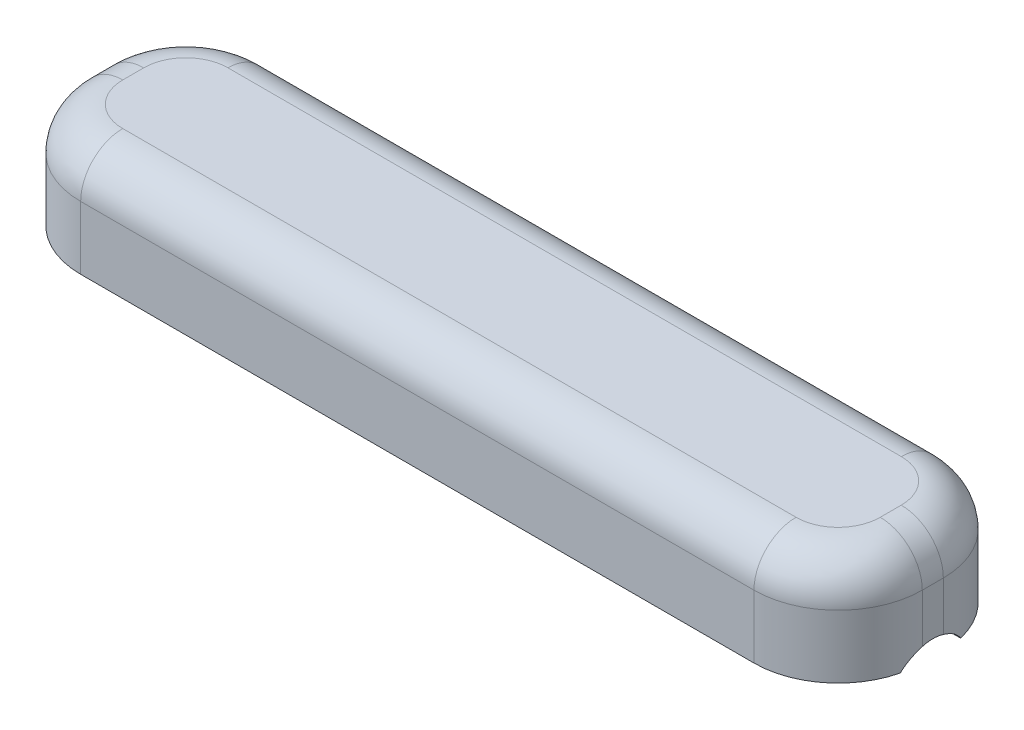
SolidWorks part; units mm, degrees
ref_plane "Front Plane" through (0, 0, 0) normal (0, 0, 1) x (1, 0, 0)
ref_plane "Top Plane" through (0, 0, 0) normal (0, 1, 0) x (1, 0, 0)
ref_plane "Right Plane" through (0, 0, 0) normal (1, 0, 0) x (0, 0, -1)
sketch "Sketch1" plane through (0, 0, 0) normal (0, 1, 0) x (1, 0, 0)
  line L1 (-127, 28.575) -> (127, 28.575)
  line L2 (-127, 28.575) -> (-127, -28.575)
  line L3 (-127, -28.575) -> (127, -28.575)
  line L4 (127, 28.575) -> (127, -28.575)
  line L5 (-127, 28.575) -> (127, -28.575) construction
  line L6 (-127, -28.575) -> (127, 28.575) construction
  point P0 (0, 0)
  dimension "D1" = 254
  dimension "D2" = 57.15
extrude "Boss-Extrude1" add sketch "Sketch1" along normal blind 31.75
fillet "Fillet1" radius 12.7 4 edges at (-127, 31.75, 0) (0, 31.75, -28.575) (127, 31.75, 0) (0, 31.75, 28.575)
fillet "Fillet2" radius 25.4 8 edges at (123.2803, 28.0303, 24.8553) (123.2803, 28.0303, -24.8553) (-123.2803, 28.0303, 24.8553) (-123.2803, 28.0303, -24.8553) (-127, 9.525, -28.575) (-127, 9.525, 28.575) (127, 9.525, -28.575) (127, 9.525, 28.575)
sketch "Sketch2" plane through (0, 0, 0) normal (1, 0, 0) x (0, 0, -1)
  line L0 (0, -6.35) -> (0, 0) construction
  circle A0 centre (0, -6.35) radius 11.1125
  dimension "D1" = 22.225
  dimension "D2" = 6.35
extrude "Cut-Extrude1" cut sketch "Sketch2" against normal through all and the other way through all
